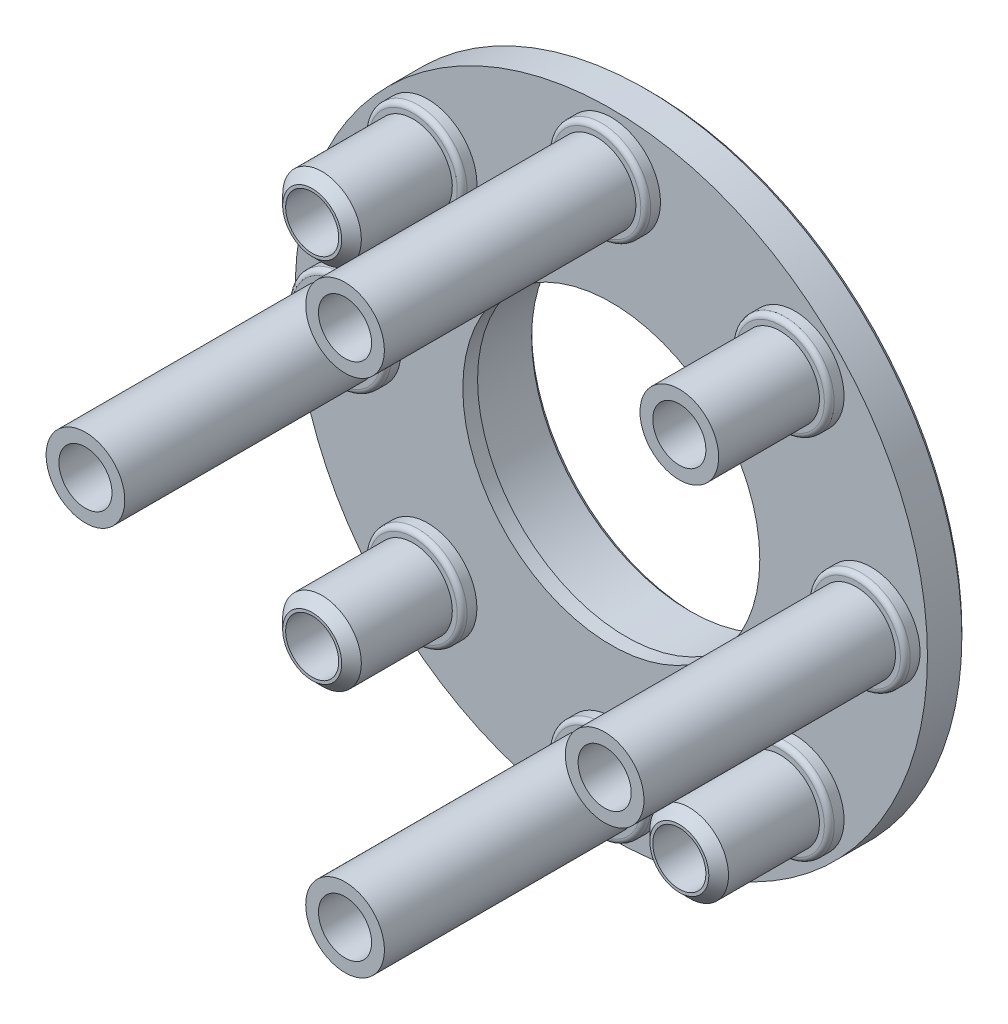
SolidWorks part; units mm, degrees
material "PLA"
ref_plane "Front Plane" through (0, 0, 0) normal (0, 0, 1) x (1, 0, 0)
ref_plane "Top Plane" through (0, 0, 0) normal (0, 1, 0) x (1, 0, 0)
ref_plane "Right Plane" through (0, 0, 0) normal (1, 0, 0) x (0, 0, -1)
sketch "Sketch1" plane through (0, 0, 0) normal (0, 0, 1) x (1, 0, 0)
  circle A0 centre (0, 0) radius 32.15
  circle A1 centre (0, 0) radius 26.4 construction
  circle A2 centre (0, 26.4) radius 2.7
  circle A3 centre (26.4, 0) radius 2.7
  circle A78 centre (0, -26.4) radius 2.7
  circle A79 centre (0, 26.4) radius 4.25 construction
  circle A80 centre (0, 0) radius 30.65 construction
  circle A94 centre (-26.4, 0) radius 2.7
  point P15 (0, 0)
  dimension "D2" = 52.8
  dimension "D3" = 5.4
  dimension "D5" = 8.5
  dimension "D4" = 4
extrude "Boss-Extrude1" add sketch "Sketch1" along normal blind 4
sketch "Sketch2" plane through (0, 0, 4) normal (0, 0, 1) x (1, 0, 0)
  circle A0 centre (0, 26.4) radius 4
  circle A2 centre (0, 26.4) radius 2.7 construction
  circle A5 centre (0, 26.4) radius 2.7
  point P15 (0, 0)
  dimension "D1" = 8
extrude "Boss-Extrude2" add sketch "Sketch2" along normal blind 27.0755
sketch "Sketch3" plane through (0, 0, 4) normal (0, 0, 1) x (1, 0, 0)
  arc A2 (5, 26.4) -> (5, 26.4) centre (0, 26.4) ccw
  circle A3 centre (0, 26.4) radius 5
  circle M5 centre (0, 26.4) radius 4
extrude "Boss-Extrude3" add sketch "Sketch3" along normal blind 1.5 contours A3 M5 region at (-4.8586, 26.4, 4)
sketch "Sketch4" plane through (0, 0, 4) normal (0, 0, 1) x (1, 0, 0)
  line L0 (0, 0) -> (-22.7335, 22.7335) construction
  line L1 (0, 0) -> (0, 26.4) construction
  circle A0 centre (0, 0) radius 32.15 construction
  circle A1 centre (0, 0) radius 32.15
  circle A2 centre (0, 26.4) radius 12 construction
  circle A6 centre (0, 0) radius 26.4 construction
  arc A8 (-13.1794, 29.3245) -> (-9.5682, 16.8763) centre (0, 26.4) ccw
  circle A9 centre (0, 0) radius 19.4
  circle A11 centre (0, 0) radius 14.4 construction
  arc A13 (-29.3245, 13.1794) -> (-16.8763, 9.5682) centre (-26.4, 0) cw
  circle A16 centre (0, 26.4) radius 13.5 construction
  point P15 (0, 0)
  point P25 (0, 0)
  dimension "D1" = 24
  dimension "D5" = 28.8
  dimension "D4" = 5
  dimension "D2" = 45
  dimension "D3" = 1.5
extrude "Boss-Extrude4" [suppressed] add sketch "Sketch4" along normal blind 27.0755 contours A1 A13 A9 A8
sketch "Sketch12" [suppressed] plane through (0, 0, 37.8382) normal (0, 0, 1) x (1, 0, 0)
  arc A0 (-11.2345, 15.816) -> (-15.816, 11.2345) centre (0, 0) ccw construction
  arc A1 (-11.2345, 15.816) -> (-15.816, 11.2345) centre (0, 0) ccw
  dimension "D1" = 6.4791
fillet "Fillet2" radius 0.5 1 edges at (5, 26.4, 5.5)
fillet "Fillet5" [suppressed] radius 1.6198
pattern_circular "CirPattern1" count 8 over 360 about axis through (0, 0, 4) along (0, 0, -1) of "Fillet2", "Boss-Extrude3", "Boss-Extrude2" reverse direction yes
ref_plane "Plane1" through (0, 0, 31.0755) normal (0, 0, 1) x (1, 0, 0)
chamfer "Chamfer1" distance 0.5 angle 45 1 edges at (32.15, 0, 0)
sketch "Sketch9" plane through (0, 0, 4) normal (0, 0, 1) x (1, 0, 0)
  circle A0 centre (0, 0) radius 8
  dimension "D1" = 16
extrude "Cut-Extrude4" cut sketch "Sketch9" against normal through all
sketch "Sketch10" plane through (0, 0, 0) normal (0, 0, -1) x (-1, 0, 0)
  circle A0 centre (0, 0) radius 8 construction
  circle A1 centre (0, 0) radius 8
  circle A2 centre (0, 0) radius 6.5
extrude "Boss-Extrude7" add sketch "Sketch10" against normal blind 6.5
sketch "Sketch13" plane through (0, 0, 0) normal (0, 1, 0) x (1, 0, 0)
  line L0 (0, 0) -> (0, -31.0755) construction
  line L1 (-4, -31.0755) -> (4, -31.0755) construction
  line L2 (15.9676, -4) -> (21.3676, -4) construction
  line L3 (-30, 0.5) -> (-39.8, -4) construction
  line L4 (-36.2054, -4) -> (-27.4943, 0)
  line L7 (31.65, 0) -> (-31.65, 0) construction
  line L8 (0, -4) -> (-39.8, -4) construction
  line L9 (-27.4943, 0) -> (-36.2054, 0)
  line L10 (-36.2054, 0) -> (-36.2054, -4)
  dimension "D1" = 30
  dimension "D2" = 39.8
  dimension "D3" = 4.5
  dimension "D4" = 1.5
sketch "Sketch14" plane through (0, 0, 4) normal (0, 0, 1) x (1, 0, 0)
  circle A0 centre (0, 0) radius 16.1
  circle A1 centre (0, 0) radius 6.5 construction
  dimension "D1" = 32.2
extrude "Cut-Extrude5" cut sketch "Sketch14" against normal through all both and the other way through all
sketch "Sketch15" plane through (0, 0, 4) normal (0, 0, 1) x (1, 0, 0)
  circle A0 centre (0, 0) radius 16.1
  circle A1 centre (0, 0) radius 15.1
  circle A2 centre (0, 0) radius 16.1 construction
  dimension "D1" = 1
extrude "Boss-Extrude8" add sketch "Sketch15" against normal blind 1.5
sketch "Sketch16" plane through (0, 0, 0) normal (0, 0, -1) x (-1, 0, 0)
  circle A0 centre (0, 0) radius 18.1
  circle A1 centre (0, 0) radius 16.1 construction
  circle M1 centre (0, 0) radius 16.1
extrude "Boss-Extrude9" add sketch "Sketch16" along normal blind 4.5 contours A0 M1 region at (17.5881, 0, 0)
chamfer "Chamfer3" distance 2 distance2 4.5 1 edges at (18.1, 0, 0) first distance on face at (18.1, 0, 0)
sketch "Sketch5" [suppressed] plane through (0, 0, 32.8234) normal (0, 0, 1) x (1, 0, 0)
  line L0 (0, 0) -> (-22.4506, 22.4506) construction
  line L1 (0, 0) -> (0, 26) construction
  circle A3 centre (-19.6222, 19.6222) radius 1.7
  circle A4 centre (0, 0) radius 31.75 construction
  arc A5 (-13.189, 28.881) -> (-28.881, 13.189) centre (0, 0) ccw construction
  dimension "D2" = 3.4
  dimension "D1" = 4
  dimension "D3" = 45
extrude "Cut-Extrude1" [suppressed] cut sketch "Sketch5" against normal through all
sketch "Sketch7" plane through (0, 0, 0) normal (0, 0, -1) x (-1, 0, 0)
  circle A0 centre (0, 26.4) radius 4.45
  circle A1 centre (0, 0) radius 26.4 construction
  point P15 (0, 0)
  dimension "D1" = 8.9
extrude "Cut-Extrude3" cut sketch "Sketch7" against normal blind 5 and the other way through all
sketch "Sketch6" [suppressed] plane through (0, 0, 0) normal (0, 0, -1) x (-1, 0, 0)
  circle A0 centre (19.6222, 19.6222) radius 2.95
  dimension "D1" = 5.9
extrude "Cut-Extrude2" [suppressed] cut sketch "Sketch6" against normal blind 3 and the other way through all
pattern_circular "CirPattern2" count 8 over 360 about axis through (0, 0, 4) along (0, 0, -1) of "Cut-Extrude3" reverse direction yes
chamfer "Chamfer4" distance 0.5 angle 45 1 edges at (-16.1, 0, -4.5)
sketch "Sketch17" plane through (0, 0, 31.0755) normal (0, 0, 1) x (1, 0, 0)
  circle A0 centre (-18.6676, 18.6676) radius 6.5962
extrude "Cut-Extrude6" cut sketch "Sketch17" against normal blind 15.3255
pattern_circular "CirPattern3" count 4 over 360 about axis through (0, 0, 4) along (0, 0, 1) of "Cut-Extrude6"
chamfer "Chamfer5" distance 1 angle 45 3 edges at (22.6676, -18.6676, 15.75) (-14.6676, 18.6676, 15.75) (-14.6676, -18.6676, 15.75)
equation "\"Nr_s\" = 116"
equation "\"module\" = 0.6"
equation "\"pressure_angle\" = 20.0"
equation "\"h_a\" = 0.6"
equation "\"h_f\" = 0.75"
equation "\"clr_tip_root\" = 0.15000000000000002"
equation "\"dp_r_s\" = 69.6"
equation "\"db_r\"= \"dp_r_s\" * cos ( \"pressure_angle\" )'base CD"
equation "\"bearing_ID\" = 60"
equation "\"bearing_OD\" = 78"
equation "\"bearing_height\" = 10"
equation "\"clearance_planet\" = 1.5"
equation "\"case_dist\" = 6.5"
equation "\"Motor_case_OD_max\" = 101.3"
equation "\"case_mounting_PCD\" = 93.8"
equation "\"bearing mount thickness\" = 8"
equation "\"case_mounting_hole_dia\" = 3"
equation "\"output_mounting_PCD\" = 86"
equation "\"output_mounting_hole_dia\" = 4"
equation "\"clearance_case_mount_holes_shell_thickness\" = 1"
equation "\"motor_case_OD_base\" = 91.8"
equation "\"sec_carrier_thickness\" = 5"
equation "\"sun_coupler_hub_thickness\" = 4"
equation "\"clearance_sun_coupler_sec_carrier\" = 1.5"
equation "\"clearance_motor_and_case\" = 7.399999999999999"
equation "\"motor_OD\" = 72"
equation "\"Motor_case_thickness\" = 2.5"
equation "\"Motor_case_ID\" = 86.8"
equation "\"case_mounting_hole_shift\" = 1.0"
equation "\"output_mounting_nut_wrench_size\" = 7"
equation "\"output_mounting_nut_thickness\" = 3.2"
equation "\"case_mounting_hole_allen_socket_dia\" = 5.5"
equation "\"output_mounting_nut_depth\" = 3"
equation "\"case_mounting_bolt_depth\" = 4.5"
equation "\"Ns\" = 48"
equation "\"Np_b\" = 40"
equation "\"ring_radial_thickness\" = 5"
equation "\"ring_OD\"= \"Nr_s\" * \"module\" + \"ring_radial_thickness\" * 2"
equation "\"ring_to_chamfer_clearance\" = 1.5"
equation "\"Motor_case_OD_base_to_chamfer\" = 5"
equation "\"pattern_offset_from_motor_case_OD_base\" = 3"
equation "\"pattern_bulge_dia\" = 3"
equation "\"pattern_num_bulge\" = 18"
equation "\"pattern_depth\" = 2"
equation "\"motor_height\" = 27"
equation "\"case_mounting_wrench_size\" = 5.5"
equation "\"case_mounting_nut_clearance\" = 2"
equation "\"base_plate_thickness\" = 4"
equation "\"case_mounting_nut_thickness\" = 2.4"
equation "\"case_mounting_surface_height\" = 4"
equation "\"motor_mount_hole_PCD\" = 32"
equation "\"motor_mount_hole_dia\" = 4"
equation "\"motor_mount_hole_num\" = 4"
equation "\"central_hole_offset_from_motor_mount_PCD\" = 5"
equation "\"wire_slot_dist_from_center\" = 26"
equation "\"wire_slot_length\" = 10"
equation "\"wire_slot_radius\" = 2.5"
equation "\"driver_upper_holes_dist_from_center\" = 29"
equation "\"driver_lower_holes_dist_from_center\" = 13"
equation "\"driver_side_holes_dist_from_center\" = 22.5"
equation "\"driver_mount_holes_dia\" = 3"
equation "\"driver_mount_inserts_OD\" = 4.8"
equation "\"driver_mount_thickness\" = 1.5"
equation "\"driver_mount_height\" = 6"
equation "\"air_flow_hole_offset\" = 3"
equation "\"num_planet\" = 4"
equation "\"planet_pin_bolt_dia\" = 5"
equation "\"planet_pin_socket_head_dia\" = 8.5"
equation "\"carrier_PCD\" = 52.8"
equation "\"D2@Sketch1\"=\"carrier_PCD\""
equation "\"D3@Sketch1\"=\"planet_pin_bolt_dia\" + \"tight_clearance_3DP\""
equation "\"D4@Sketch1\"=\"num_planet\""
equation "\"D1@Boss-Extrude2\" = \"fw_p_s\" + \"clearance_planet\" * 2 + \"fw_p_b\""
equation "\"D1@Boss-Extrude3\"=\"clearance_planet\""
equation "\"D1@Sketch4\"=\"Np_b\"*\"module\""
equation "\"D3@Sketch4\"=\"clearance_planet\""
equation "\"D1@Boss-Extrude4\" = \"fw_p_s\" + \"clearance_planet\" * 2 + \"fw_p_b\""
equation "\"D1@Fillet2\"=\"clearance_planet\"/3"
equation "\"D1@CirPattern1\"=2*\"num_planet\""
equation "\"D1@CirPattern2\"=2*\"num_planet\""
equation "\"D1@Boss-Extrude7\"=\"bearing_height\"+ \"carrier_bearing_step_width\" - \"sun_shaft_bearing_width\""
equation "\"planet_shaft_dia\" = 8"
equation "\"D1@Sketch2\"= \"planet_shaft_dia\""
equation "\"planet_shaft_step_offset\" = 1"
equation "\"D1@Sketch3\"=\"planet_shaft_step_offset\""
equation "\"carrier_trapezoidal_support_sun_offset\" = 5"
equation "\"D4@Sketch4\"=\"carrier_trapezoidal_support_sun_offset\""
equation "\"carrier_trapezoidal_support_hole_PCD_offset_bearing_ID\" = 4"
equation "\"carrier_trapezoidal_support_hole_dia\" = 3"
equation "\"D2@Sketch5\"=\"carrier_trapezoidal_support_hole_dia\" + \"tight_clearance_3DP\""
equation "\"D1@Cut-Extrude2\"=\"carrier_trapezoidal_support_hole_dia\""
equation "\"carrier_trapezoidal_support_hole_socket_head_dia\" = 5.5"
equation "\"D1@Sketch6\"=\"carrier_trapezoidal_support_hole_socket_head_dia\" +  \"tight_clearance_3DP\""
equation "\"D1@Cut-Extrude3\"=\"planet_pin_bolt_dia\""
equation "\"D1@Sketch7\"=\"planet_pin_socket_head_dia\" + \"tight_clearance_3DP\""
equation "\"carrier_bearing_step_width\" = 1.5"
equation "\"standard_clearance_1_5mm\" = 1.5"
equation "\"standard_fillet_1_5mm\" = 1.5"
equation "\"sun_shaft_bearing_OD\" = 16"
equation "\"D1@Sketch9\"=\"sun_shaft_bearing_OD\""
equation "\"D1@Sketch10\"=\"standard_clearance_1_5mm\""
equation "\"sun_shaft_bearing_width\" = 5"
equation "\"standard_bearing_insertion_chamfer\" = 0.5"
equation "\"D1@Chamfer1\"=\"standard_bearing_insertion_chamfer\""
equation "\"D5@Sketch4\"=\"Ns\"*\"module\""
equation "\"D1@Sketch5\"=\"carrier_trapezoidal_support_hole_PCD_offset_bearing_ID\""
equation "\"D1@Plane1\" = \"fw_p_s\" + \"clearance_planet\" * 2 + \"fw_p_b\""
equation "\"D2@Sketch4\"=180/\"num_planet\""
equation "\"D3@Sketch5\"=180/\"num_planet\""
equation "\"carrier_trapezoidal_support_hole_wrench_size\" = 5.5"
equation "\"planet_pin_bolt_wrench_size\" = 8"
equation "\"pressure angle\" = 20.0"
equation "\"h_b\" = 0.75"
equation "\"dp_s\" = 28.799999999999997"
equation "\"db_s\" = 27.06314747863416"
equation "\"fw_s_calc\" = 2.359230083666351"
equation "\"alpha_s\" = 0.8539582918412343"
equation "\"beta_s\" = 2.0420834163175314"
equation "\"dp_p_b\" = 24.0"
equation "\"db_p_b\" = 22.552622898861802"
equation "\"fw_p_s\" = 11.6295029769434"
equation "\"alpha_p_b\" = 0.8539582918412414"
equation "\"beta_p_b\" = 2.792083416317517"
equation "\"planet_bearing_OD\" = 12"
equation "\"planet_bearing_width\" = 3.5"
equation "\"planet_bore\" = 10"
equation "\"motor_output_hole_PCD\" = 22"
equation "\"motor_output_hole_dia\" = 3"
equation "\"motor_output_hole_num\" = 4"
equation "\"sun_shaft_bearing_ID\" = 8"
equation "\"sun_hub_dia\" = 28.0"
equation "\"sun_central_bolt_dia\" = 5"
equation "\"sun_central_bolt_socket_head_dia\" = 8.5"
equation "\"fw_s_used\" = 31.575468444261382"
equation "\"motor_output_hole_CSK_OD\" = 6"
equation "\"motor_output_hole_CSK_head_height\" = 1.5"
equation "\"bearing_retainer_thickness\" = 2"
equation "\"Np_s\" = 28"
equation "\"fw_p_b\" = 12.445965467317981"
equation "\"dp_p_s\" = 16.8"
equation "\"db_p_s\" = 15.786836029203263"
equation "\"alpha_p_s\" = 0.8539582918412343"
equation "\"beta_p_s\" = 4.72065484488896"
equation "\"D1@Fillet5\"= \"D1@Sketch12\" / 4"
equation "\"Nr_b\" = 128"
equation "\"dp_r_b\" = 76.8"
equation "\"db_r_b\" = 72.16839327635776"
equation "\"fw_r_b\" = 12.445965467317981"
equation "\"alpha_r_b\" = 0.8539582918412556"
equation "\"beta_r_b\" = 3.114166583682511"
equation "\"ring_OD_b\" = 86.8"
equation "\"Fillet10\"= IIF ( \"ring_OD_b\" > ( \"bearing_OD\" + 2 * \"bearing mount thickness\" ) , \"suppressed\" , \"unsuppressed\" )"
equation "\"Fillet11\"= IIF ( \"ring_OD_b\" < ( \"bearing_OD\" + 2 * \"bearing mount thickness\" ) , \"suppressed\" , \"unsuppressed\" )"
equation "\"clr_tip_root_s\" = 0.15000000000000002"
equation "\"db_r_s\" = 65.40260640669922"
equation "\"fw_r_s\" = 10.1295029769434"
equation "\"alpha_r_s\" = 0.8539582918412343"
equation "\"beta_r_s\" = 3.2596407216135033"
equation "\"D1@Sketch13\"=\"bearing_ID\"/2"
equation "\"D2@Sketch13\"=(\"Nr_s\"*\"module\"+\"ring_radial_thickness\"*2)*0.5"
equation "\"D3@Sketch13\"=\"standard_clearance_1_5mm\"*3"
equation "\"D4@Sketch13\"=\"standard_clearance_1_5mm\""
equation "\"D5@Sketch1\"=\"planet_pin_socket_head_dia\""
equation "\"D1@Sketch1\"=\"standard_clearance_1_5mm\""
equation "\"small_ring_case_thickness\" = 4"
equation "\"carrier_thickness\" = 4"
equation "\"small_ring_output_wall_thickness\" = 5"
equation "\"small_ring_output_wall_to_bearing_shaft_attachement_hole_dia\" = 4"
equation "\"small_ring_output_wall_to_bearing_shaft_attachement_hole_depth\" = 6.5"
equation "\"small_ring_output_wall_to_bearing_shaft_attachement_nut_wrench\" = 7"
equation "\"small_ring_output_wall_to_bearing_shaft_attachement_nut_thickness\" = 3.2"
equation "\"small_ring_output_wall_to_bearing_shaft_attachement_hole_pcd\" = 12"
equation "\"small_ring_output_wall_to_bearing_shaft_attachement_hole_num\" = 3"
equation "\"small_ring_output_wall_to_bearing_shaft_attachement_hole_CSK_OD\" = 8"
equation "\"small_ring_output_wall_to_bearing_shaft_attachement_hole_CSK_head_height\" = 2.0"
equation "\"carrier_small_ring_inner_bearing_ID\" = 20"
equation "\"carrier_small_ring_inner_bearing_OD\" = 32"
equation "\"carrier_small_ring_inner_bearing_height\" = 7"
equation "\"carrier_small_ring_inner_bearing_flap\" = 2"
equation "\"gear_casing_big_ring_to_bearing_dist\" = 20.6295029769434"
equation "\"gear_casing_thickness\" = 4"
equation "\"D1@Boss-Extrude1\"=\"carrier_thickness\""
equation "\"D1@Boss-Extrude9\"= \"carrier_small_ring_inner_bearing_height\" - \"carrier_thickness\" + \"standard_clearance_1_5mm\""
equation "\"D3@Chamfer3\"=\"carrier_small_ring_inner_bearing_height\"-\"carrier_thickness\" + \"standard_clearance_1_5mm\""
equation "\"D1@Chamfer3\"=\"standard_clearance_1_5mm\"*4/3"
equation "\"D1@Sketch14\"=\"carrier_small_ring_inner_bearing_OD\" + \"tight_clearance_3DP\"/2"
equation "\"D1@Sketch16\"=\"standard_clearance_1_5mm\"*4/3"
equation "\"tight_clearance_3DP\" = 0.4"
equation "\"loose_clearance_3DP\" = 0.8"
equation "\"D1@Chamfer4\"= \"standard_bearing_insertion_chamfer\""
equation "\"D1@Cut-Extrude6\"=\"fw_p_s\" + \"clearance_planet\" * 2 + \"fw_p_b\" - \"fw_idler\"-3mm"
equation "\"D1@CirPattern3\"=\"num_planet\""
equation "\"Ns_fs\" = 60"
equation "\"dp_fs\" = 36.0"
equation "\"db_fs\" = 33.828934348292705"
equation "\"alpha_fs\" = 0.8539582918412343"
equation "\"beta_fs\" = 1.2920834163175314"
equation "\"fw_fs\" = 11.6295029769434"
equation "\"num_idler\" = 4"
equation "\"idler_angle_offset\" = 45.0"
equation "\"fs_bore_dia\"= 31.599999999999998"
equation "\"fs_bore_wall\"= 2.6500000000000004"
equation "\"fs_axial_clearance\"= 0.8"
equation "\"fw_idler\" = 8.75"
